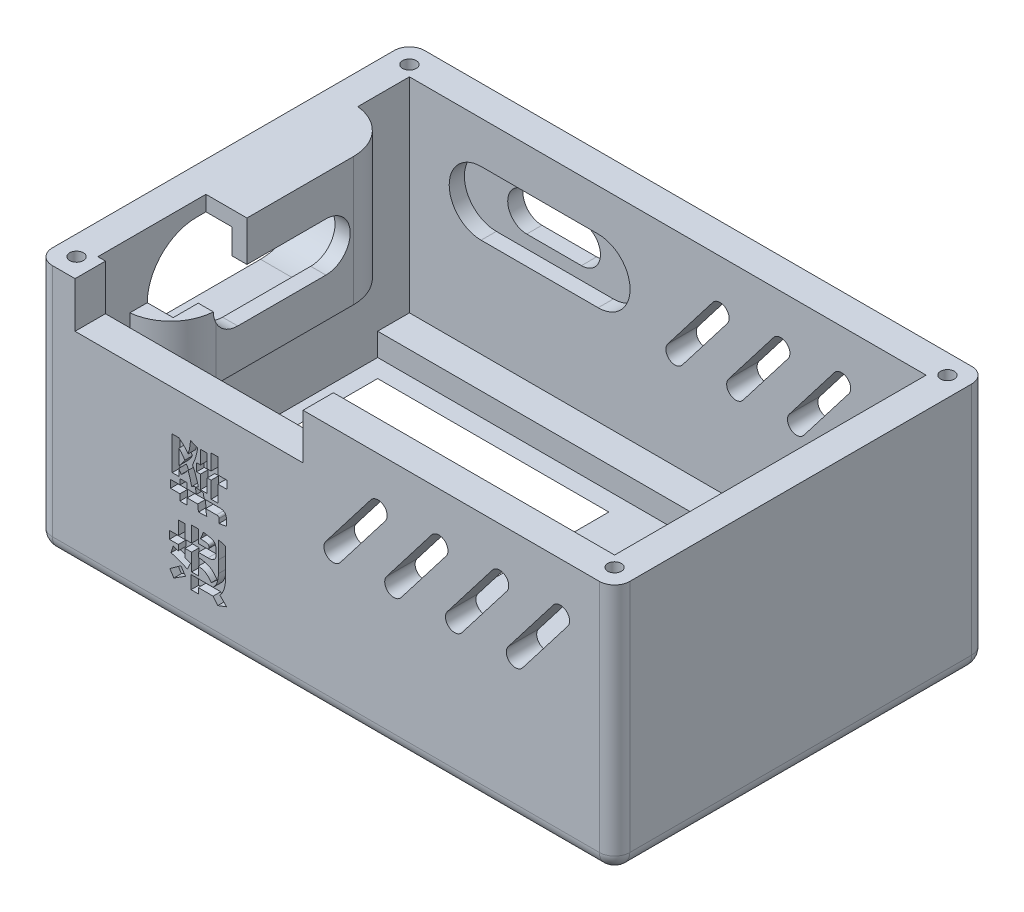
SolidWorks part; units mm, degrees
material "尼龙 6/10"
ref_plane "前视基准面" through (0, 0, 0) normal (0, 0, 1) x (1, 0, 0)
ref_plane "上视基准面" through (0, 0, 0) normal (0, 1, 0) x (1, 0, 0)
ref_plane "右视基准面" through (0, 0, 0) normal (1, 0, 0) x (0, 0, -1)
sketch "草图1" plane through (0, 0, 0) normal (0, 1, 0) x (1, 0, 0)
  line L1 (-72.1576, -30.7504) -> (-34.1576, -30.7504)
  line L2 (-72.1576, -30.7504) -> (-72.1576, -6.2504)
  line L3 (-72.1576, -6.2504) -> (-34.1576, -6.2504)
  line L4 (-34.1576, -30.7504) -> (-34.1576, -6.2504)
  dimension "D1" = 24.5
  dimension "D2" = 38
extrude "凸台-拉伸1" add sketch "草图1" along normal blind 16.45 contours L2 L1 L4 L3
sketch "草图2" plane through (0, 16.45, 0) normal (0, 1, 0) x (1, 0, 0)
  line L0 (-34.1576, -30.7504) -> (-34.1576, -6.2504) construction
  line L1 (-70.1576, -8.2504) -> (-36.1576, -8.2504)
  line L2 (-70.1576, -8.2504) -> (-70.1576, -28.7504)
  line L3 (-70.1576, -28.7504) -> (-36.1576, -28.7504)
  line L4 (-36.1576, -8.2504) -> (-36.1576, -28.7504)
  line L5 (-72.1576, -30.7504) -> (-34.1576, -30.7504) construction
  line L6 (-72.1576, -30.7504) -> (-72.1576, -6.2504) construction
  line L7 (-72.1576, -6.2504) -> (-34.1576, -6.2504) construction
  dimension "D1" = 2
  dimension "D2" = 2
  dimension "D3" = 2
  dimension "D4" = 2
extrude "切除-拉伸1" cut sketch "草图2" against normal blind 13.45
sketch "草图4" plane through (0, 0, 0) normal (0, -1, 0) x (-1, 0, 0)
  line L0 (72.1576, -30.7504) -> (72.1576, -6.2504) construction
  line L1 (68.9576, -11.5404) -> (53.7476, -11.5404)
  line L2 (68.9576, -11.5404) -> (68.9576, -26.7504)
  line L3 (68.9576, -26.7504) -> (53.7476, -26.7504)
  line L4 (53.7476, -11.5404) -> (53.7476, -26.7504)
  line L6 (72.1576, -30.7504) -> (34.1576, -30.7504) construction
  dimension "D1" = 15.21
  dimension "D2" = 15.21
  dimension "D3" = 3.2
  dimension "D4" = 4
extrude "切除-拉伸2" cut sketch "草图4" against normal blind 15 contours L2 L1 L4 L3
sketch "草图6" plane through (0, 0, 30.7504) normal (0, 0, 1) x (1, 0, 0)
  line L1 (-54.6576, 13.45) -> (-69.6576, 13.45)
  line L2 (-54.6576, 13.45) -> (-54.6576, 16.45)
  line L3 (-54.6576, 16.45) -> (-69.6576, 16.45)
  line L4 (-69.6576, 13.45) -> (-69.6576, 16.45)
  line L5 (-72.1576, 16.45) -> (-72.1576, 0) construction
  line L6 (-72.1576, 16.45) -> (-34.1576, 16.45) construction
  point P9 (-69.6576, 14.95)
  dimension "D2" = 3
  dimension "D3" = 2.5
  dimension "D4" = 15
extrude "切除-拉伸4" cut sketch "草图6" against normal blind 5
sketch "草图11" plane through (0, 3, 0) normal (0, 1, 0) x (1, 0, 0)
  line L0 (-68.9576, -26.7504) -> (-68.9576, -11.5404) construction
  line L1 (-37.6576, -10.3404) -> (-70.1576, -10.3404)
  line L2 (-37.6576, -10.3404) -> (-37.6576, -27.9404)
  line L3 (-37.6576, -27.9404) -> (-70.1576, -27.9404)
  line L4 (-70.1576, -10.3404) -> (-70.1576, -27.9404)
  line L5 (-53.7476, -11.5404) -> (-68.9576, -11.5404) construction
  line L7 (-36.1576, -28.7504) -> (-36.1576, -8.2504) construction
  dimension "D1" = 1.5
  dimension "D2" = 17.6
  dimension "D3" = 1.2
  dimension "D4" = 1.2
extrude "切除-拉伸10" cut sketch "草图11" against normal blind 1.5
fillet "圆角2" radius 1 8 edges at (-34.1576, 8.225, 6.2504) (-53.1576, 0, 6.2504) (-53.1576, 0, 30.7504) (-72.1576, 0, 18.5004) (-72.1576, 8.225, 30.7504) (-34.1576, 8.225, 30.7504) (-34.1576, 0, 18.5004) (-72.1576, 8.225, 6.2504)
chamfer "倒角2" distance 1.5 distance2 1.5 4 edges at (-61.3526, 0, 26.7504) (-53.7476, 0, 19.1454) (-61.3526, 0, 11.5404) (-68.9576, 0, 19.1454)
fillet "圆角8" radius 1 1 edges at (-37.6576, 3, 19.1404) type face fillet first side face at (-37.6576, 2.25, 19.1404) second side face at (-53.5326, 3, 18.8204)
sketch "草图24" plane through (-36.1576, 0, 0) normal (-1, 0, 0) x (0, 0, 1)
  line L1 (22.6404, 3) -> (15.6404, 3)
  line L2 (22.6404, 3) -> (22.6404, 12.5)
  line L3 (22.6404, 12.5) -> (15.6404, 12.5)
  line L4 (15.6404, 3) -> (15.6404, 12.5)
  line L10 (10.3404, 3) -> (27.9404, 3) construction
  point P4 (19.1404, 3)
  dimension "D1" = 9.5
  dimension "D2" = 7
extrude "切除-拉伸17" cut sketch "草图24" against normal blind 1
sketch "草图29" plane through (0, 16.45, 0) normal (0, 1, 0) x (1, 0, 0)
  line L0 (-72.1576, -29.7504) -> (-72.1576, -7.2504) construction
  line L4 (-34.1576, -29.7504) -> (-34.1576, -7.2504) construction
  line L5 (-71.1576, -30.7504) -> (-69.6576, -30.7504) construction
  line L8 (-71.1576, -6.2504) -> (-35.1576, -6.2504) construction
  circle A0 centre (-70.8576, -7.5504) radius 0.45
  circle A1 centre (-70.8576, -29.4504) radius 0.45
  circle A2 centre (-35.4576, -7.5504) radius 0.45
  circle A3 centre (-35.4576, -29.4504) radius 0.45
  dimension "D1" = 0.9
  dimension "D2" = 1.3
  dimension "D3" = 1.3
  dimension "D4" = 1.3
  dimension "D5" = 1.3
extrude "切除-拉伸18" cut sketch "草图29" against normal blind 6
sketch "草图32" plane through (0, 0, 8.2504) normal (0, 0, 1) x (1, 0, 0)
  line L0 (-57.7394, 11.6) -> (-65.4394, 11.6) construction
  line L1 (-57.7394, 9.5) -> (-65.4394, 9.5)
  line L2 (-57.7394, 13.7) -> (-65.4394, 13.7)
  line L4 (-36.1576, 3) -> (-70.1576, 3) construction
  arc A0 (-57.7394, 9.5) -> (-57.7394, 13.7) centre (-57.7394, 11.6) ccw
  arc A1 (-65.4394, 13.7) -> (-65.4394, 9.5) centre (-65.4394, 11.6) ccw
  point P2 (-61.5894, 11.6)
  dimension "D1" = 7.7
  dimension "D2" = 4.2
  dimension "D3" = 6.5
extrude "切除-拉伸19" cut sketch "草图32" against normal blind 1 contours L1 A1 L2 A0
sketch "草图33" plane through (0, 0, 7.2504) normal (0, 0, 1) x (1, 0, 0)
  line L0 (-63.4394, 12.85) -> (-59.8394, 12.85)
  line L1 (-59.8394, 10.35) -> (-63.4394, 10.35)
  line L6 (-57.7394, 13.7) -> (-65.4394, 13.7) construction
  arc A0 (-59.8394, 10.35) -> (-59.8394, 12.85) centre (-59.8394, 11.6) ccw
  arc A1 (-63.4394, 12.85) -> (-63.4394, 10.35) centre (-63.4394, 11.6) ccw
  arc A3 (-65.4394, 13.7) -> (-65.4394, 9.5) centre (-65.4394, 11.6) ccw construction
  dimension "D2" = 3.6
  dimension "D5" = 1.25
  dimension "D6" = 1.25
  dimension "D1" = 2.5
  dimension "D3" = 2
  dimension "D4" = 0.85
extrude "切除-拉伸20" cut sketch "草图33" against normal up to next
sketch "草图37" plane through (0, 16.45, 0) normal (0, 1, 0) x (1, 0, 0)
  line L1 (-70.4576, -11.6454) -> (-67.4576, -11.6454)
  line L2 (-70.4576, -11.6454) -> (-70.4576, -26.6454)
  line L3 (-70.4576, -26.6454) -> (-67.4576, -26.6454)
  line L4 (-67.4576, -11.6454) -> (-67.4576, -26.6454)
  line L5 (-70.4576, -10.0404) -> (-70.4576, -28.2504) construction
  point P4 (-70.4576, -19.1454)
  dimension "D1" = 3
  dimension "D2" = 15
extrude "凸台-拉伸8" add sketch "草图37" against normal blind 10
sketch "草图34" plane through (-72.1576, 0, 0) normal (-1, 0, 0) x (0, 0, 1)
  line L0 (22.2454, 12.2) -> (16.0454, 12.2) construction
  line L3 (22.2454, 8.95) -> (16.0454, 8.95)
  line L4 (22.2454, 15.45) -> (16.0454, 15.45)
  line L5 (10.0404, 0) -> (28.2504, 0) construction
  line L7 (29.7504, 16.45) -> (7.2504, 16.45) construction
  line L12 (7.2504, 1) -> (29.7504, 1) construction
  arc A2 (22.2454, 8.95) -> (22.2454, 15.45) centre (22.2454, 12.2) ccw
  arc A3 (16.0454, 15.45) -> (16.0454, 8.95) centre (16.0454, 12.2) ccw
  point P3 (19.1454, 12.2)
  point P8 (19.1454, 15.45)
  point P15 (18.5004, 1)
  point P19 (19.1454, 0)
  dimension "D3" = 1
  dimension "D1" = 6.2
  dimension "D2" = 6.5
extrude "切除-拉伸21" cut sketch "草图34" against normal blind 3.7
sketch "草图39" plane through (-68.4576, 0, 0) normal (-1, 0, 0) x (0, 0, 1)
  line L0 (22.2454, 12.2) -> (16.4454, 12.2) construction
  line L1 (22.2454, 10.6) -> (16.4454, 10.6)
  line L2 (22.2454, 13.8) -> (16.4454, 13.8)
  line L4 (22.2454, 15.45) -> (16.0454, 15.45) construction
  line L5 (16.0454, 8.95) -> (22.2454, 8.95) construction
  arc A0 (22.2454, 10.6) -> (22.2454, 13.8) centre (22.2454, 12.2) ccw
  arc A1 (16.4454, 13.8) -> (16.4454, 10.6) centre (16.4454, 12.2) ccw
  point P2 (19.3454, 12.2)
  point P7 (23.8454, 12.2)
  point P8 (14.8454, 12.2)
  dimension "D1" = 3.2
  dimension "D2" = 9
extrude "切除-拉伸24" cut sketch "草图39" against normal blind 9 contours L1 A1 L2 A0
fillet "圆角9" radius 3 2 edges at (-67.4576, 11.45, 11.6454) (-67.4576, 11.45, 26.6454)
sketch "草图42" plane through (0, 0, 6.2504) normal (0, 0, -1) x (-1, 0, 0)
  line L0 (72.1576, 16.45) -> (72.1576, 1) construction
  text T0 "<b><r270>确</r></b>" font "微软雅黑" height 3
  text T1 "<b><r270>认</r></b>" font "微软雅黑" height 3
  dimension "D1" = 12
extrude "切除-拉伸26" cut sketch "草图42" against normal blind 0.5
sketch "草图43" plane through (0, 0, 30.7504) normal (0, 0, 1) x (1, 0, 0)
  line L0 (-71.1576, 16.45) -> (-71.1576, 1) construction
  text T0 "<b><r90>选</r></b>" font "微软雅黑" height 3
  text T1 "<b><r90>择</r></b>" font "微软雅黑" height 3
  dimension "D1" = 11
extrude "切除-拉伸27" cut sketch "草图43" against normal blind 0.5
sketch "草图46" plane through (-67.4576, 0, 0) normal (1, 0, 0) x (0, 0, -1)
  line L19 (-26.6454, 8) -> (-11.6454, 8)
  line L20 (-26.6454, 8) -> (-26.6454, 3)
  line L21 (-26.6454, 3) -> (-11.6454, 3)
  line L22 (-11.6454, 8) -> (-11.6454, 3)
  line L25 (-8.2504, 3) -> (-10.3404, 3) construction
  dimension "D1" = 5
extrude "切除-拉伸29" cut sketch "草图46" against normal up to surface (2.7 mm away) and the other way up to surface (31.3 mm away) up to face at (-70.1576, 7.8083, 18.9288) other way up to face at (-36.1576, 8.7375, 18.8204)
sketch "草图48" plane through (0, 1.5, 0) normal (0, 1, 0) x (1, 0, 0)
  line L0 (-70.1576, -8.2504) -> (-70.1576, -10.3404) construction
  line L1 (-49.3076, -10.9679) -> (-47.5264, -10.9679)
  line L2 (-49.3076, -10.9679) -> (-49.3076, -12.9679)
  line L3 (-49.3076, -12.9679) -> (-47.5264, -12.9679)
  line L4 (-47.5264, -10.9679) -> (-47.5264, -12.9679)
  line L5 (-49.3076, -25.3179) -> (-47.5264, -25.3179)
  line L6 (-49.3076, -25.3179) -> (-49.3076, -27.3179)
  line L7 (-49.3076, -27.3179) -> (-47.5264, -27.3179)
  line L8 (-47.5264, -25.3179) -> (-47.5264, -27.3179)
  dimension "D1" = 20.85
  dimension "D2" = 2
  dimension "D3" = 12.35
extrude "凸台-拉伸9" add sketch "草图48" along normal blind 1.4
sketch "草图49" plane through (0, 3, 0) normal (0, 1, 0) x (1, 0, 0)
  line L1 (-36.6576, -15.6404) -> (-37.6576, -15.6404)
  line L2 (-36.6576, -15.6404) -> (-36.6576, -22.6404)
  line L3 (-36.6576, -22.6404) -> (-37.6576, -22.6404)
  line L4 (-37.6576, -15.6404) -> (-37.6576, -22.6404)
  line L5 (-37.6576, -27.9404) -> (-37.6576, -10.3404) construction
  line L11 (-36.6576, -10.3404) -> (-36.6576, -27.9404) construction
  point P4 (-36.6576, -19.1404)
  dimension "D1" = 7
extrude "切除-拉伸30" cut sketch "草图49" against normal up to surface (1.5 mm away) up to face at (-48.417, 1.5, 11.9679)
sketch "草图50" plane through (0, 0, 6.2504) normal (0, 0, -1) x (-1, 0, 0)
  line L0 (49.7213, 13.2108) -> (52.6822, 9.3661) construction
  line L1 (50.1967, 13.5769) -> (53.1576, 9.7322)
  line L2 (49.2459, 12.8448) -> (52.2068, 9)
  line L3 (45.7213, 13.2108) -> (48.6822, 9.3661) construction
  line L4 (46.1967, 13.5769) -> (49.1576, 9.7322)
  line L5 (45.2459, 12.8448) -> (48.2068, 9)
  line L6 (41.7213, 13.2108) -> (44.6822, 9.3661) construction
  line L7 (42.1967, 13.5769) -> (45.1576, 9.7322)
  line L8 (41.2459, 12.8448) -> (44.2068, 9)
  line L9 (37.7213, 13.2108) -> (40.6822, 9.3661) construction
  line L10 (38.1967, 13.5769) -> (41.1576, 9.7322)
  line L11 (37.2459, 12.8448) -> (40.2068, 9)
  line L12 (71.1576, 1) -> (71.1576, 16.45) construction
  line L13 (35.1576, 1) -> (71.1576, 1) construction
  arc A0 (50.1967, 13.5769) -> (49.2459, 12.8448) centre (49.7213, 13.2108) ccw
  arc A1 (52.2068, 9) -> (53.1576, 9.7322) centre (52.6822, 9.3661) ccw
  arc A2 (46.1967, 13.5769) -> (45.2459, 12.8448) centre (45.7213, 13.2108) ccw
  arc A3 (48.2068, 9) -> (49.1576, 9.7322) centre (48.6822, 9.3661) ccw
  arc A4 (42.1967, 13.5769) -> (41.2459, 12.8448) centre (41.7213, 13.2108) ccw
  arc A5 (44.2068, 9) -> (45.1576, 9.7322) centre (44.6822, 9.3661) ccw
  arc A6 (38.1967, 13.5769) -> (37.2459, 12.8448) centre (37.7213, 13.2108) ccw
  arc A7 (40.2068, 9) -> (41.1576, 9.7322) centre (40.6822, 9.3661) ccw
  point P2 (51.2018, 11.2885)
  point P11 (47.2018, 11.2885)
  point P18 (43.2018, 11.2885)
  point P25 (39.2018, 11.2885)
  dimension "D4" = 4.8527
  dimension "D2" = 18
  dimension "D3" = 8
  dimension "D1" = 4
extrude "切除-拉伸31" cut sketch "草图50" against normal through all
sketch "草图51" plane through (0, 0, 0) normal (0, -1, 0) x (1, 0, 0)
  line L0 (-50.2476, 28.2504) -> (-48.2476, 28.2504)
  line L1 (-39.1576, 28.2504) -> (-37.1576, 28.2504)
  line L2 (-39.1576, 28.2504) -> (-39.1576, 9.2504)
  line L3 (-39.1576, 9.2504) -> (-37.1576, 9.2504)
  line L4 (-37.1576, 28.2504) -> (-37.1576, 9.2504)
  line L5 (-50.2476, 28.2504) -> (-50.2476, 9.2504)
  line L6 (-50.2476, 9.2504) -> (-48.2476, 9.2504)
  line L7 (-48.2476, 28.2504) -> (-48.2476, 9.2504)
  line L8 (-52.2476, 28.2504) -> (-52.2476, 10.0404) construction
  line L9 (-35.1576, 7.2504) -> (-35.1576, 29.7504) construction
  line L10 (-71.1576, 7.2504) -> (-35.1576, 7.2504) construction
  line L11 (-70.4576, 28.2504) -> (-52.2476, 28.2504) construction
  dimension "D1" = 2
  dimension "D2" = 2
  dimension "D4" = 2
  dimension "D5" = 2
extrude "切除-拉伸32" cut sketch "草图51" against normal blind 0.5
sketch "草图52" plane through (0, 0.5, 0) normal (0, -1, 0) x (1, 0, 0)
  line L0 (-50.2476, 28.2504) -> (-50.2476, 9.2504) construction
  line L1 (-50.2476, 27.9504) -> (-48.2476, 27.9504)
  line L2 (-50.2476, 27.9504) -> (-50.2476, 27.4504)
  line L3 (-50.2476, 27.4504) -> (-48.2476, 27.4504)
  line L4 (-48.2476, 27.9504) -> (-48.2476, 27.4504)
  line L5 (-48.2476, 9.2504) -> (-48.2476, 28.2504) construction
  line L6 (-48.2476, 28.2504) -> (-50.2476, 28.2504) construction
  line L7 (-39.1576, 27.9504) -> (-39.1576, 27.4504)
  line L8 (-39.1576, 27.9504) -> (-37.1576, 27.9504)
  line L9 (-37.1576, 27.9504) -> (-37.1576, 27.4504)
  line L10 (-39.1576, 27.4504) -> (-37.1576, 27.4504)
  line L11 (-39.1576, 27.1231) -> (-39.1576, 26.6231)
  line L12 (-39.1576, 27.1231) -> (-37.1576, 27.1231)
  line L13 (-37.1576, 27.1231) -> (-37.1576, 26.6231)
  line L14 (-39.1576, 26.6231) -> (-37.1576, 26.6231)
  line L15 (-39.1576, 26.2959) -> (-39.1576, 25.7959)
  line L16 (-39.1576, 26.2959) -> (-37.1576, 26.2959)
  line L17 (-37.1576, 26.2959) -> (-37.1576, 25.7959)
  line L18 (-39.1576, 25.7959) -> (-37.1576, 25.7959)
  line L19 (-39.1576, 25.4686) -> (-39.1576, 24.9686)
  line L20 (-39.1576, 25.4686) -> (-37.1576, 25.4686)
  line L21 (-37.1576, 25.4686) -> (-37.1576, 24.9686)
  line L22 (-39.1576, 24.9686) -> (-37.1576, 24.9686)
  line L23 (-39.1576, 24.6413) -> (-39.1576, 24.1413)
  line L24 (-39.1576, 24.6413) -> (-37.1576, 24.6413)
  line L25 (-37.1576, 24.6413) -> (-37.1576, 24.1413)
  line L26 (-39.1576, 24.1413) -> (-37.1576, 24.1413)
  line L27 (-39.1576, 23.8141) -> (-39.1576, 23.3141)
  line L28 (-39.1576, 23.8141) -> (-37.1576, 23.8141)
  line L29 (-37.1576, 23.8141) -> (-37.1576, 23.3141)
  line L30 (-39.1576, 23.3141) -> (-37.1576, 23.3141)
  line L31 (-39.1576, 22.9868) -> (-39.1576, 22.4868)
  line L32 (-39.1576, 22.9868) -> (-37.1576, 22.9868)
  line L33 (-37.1576, 22.9868) -> (-37.1576, 22.4868)
  line L34 (-39.1576, 22.4868) -> (-37.1576, 22.4868)
  line L35 (-39.1576, 22.1595) -> (-39.1576, 21.6595)
  line L36 (-39.1576, 22.1595) -> (-37.1576, 22.1595)
  line L37 (-37.1576, 22.1595) -> (-37.1576, 21.6595)
  line L38 (-39.1576, 21.6595) -> (-37.1576, 21.6595)
  line L39 (-39.1576, 21.3322) -> (-39.1576, 20.8322)
  line L40 (-39.1576, 21.3322) -> (-37.1576, 21.3322)
  line L41 (-37.1576, 21.3322) -> (-37.1576, 20.8322)
  line L42 (-39.1576, 20.8322) -> (-37.1576, 20.8322)
  line L43 (-39.1576, 20.505) -> (-39.1576, 20.005)
  line L44 (-39.1576, 20.505) -> (-37.1576, 20.505)
  line L45 (-37.1576, 20.505) -> (-37.1576, 20.005)
  line L46 (-39.1576, 20.005) -> (-37.1576, 20.005)
  line L47 (-39.1576, 19.6777) -> (-39.1576, 19.1777)
  line L48 (-39.1576, 19.6777) -> (-37.1576, 19.6777)
  line L49 (-37.1576, 19.6777) -> (-37.1576, 19.1777)
  line L50 (-39.1576, 19.1777) -> (-37.1576, 19.1777)
  line L51 (-39.1576, 18.8504) -> (-39.1576, 18.3504)
  line L52 (-39.1576, 18.8504) -> (-37.1576, 18.8504)
  line L53 (-37.1576, 18.8504) -> (-37.1576, 18.3504)
  line L54 (-39.1576, 18.3504) -> (-37.1576, 18.3504)
  line L55 (-39.1576, 18.0231) -> (-39.1576, 17.5231)
  line L56 (-39.1576, 18.0231) -> (-37.1576, 18.0231)
  line L57 (-37.1576, 18.0231) -> (-37.1576, 17.5231)
  line L58 (-39.1576, 17.5231) -> (-37.1576, 17.5231)
  line L59 (-39.1576, 17.1959) -> (-39.1576, 16.6959)
  line L60 (-39.1576, 17.1959) -> (-37.1576, 17.1959)
  line L61 (-37.1576, 17.1959) -> (-37.1576, 16.6959)
  line L62 (-39.1576, 16.6959) -> (-37.1576, 16.6959)
  line L63 (-39.1576, 16.3686) -> (-39.1576, 15.8686)
  line L64 (-39.1576, 16.3686) -> (-37.1576, 16.3686)
  line L65 (-37.1576, 16.3686) -> (-37.1576, 15.8686)
  line L66 (-39.1576, 15.8686) -> (-37.1576, 15.8686)
  line L67 (-39.1576, 15.5413) -> (-39.1576, 15.0413)
  line L68 (-39.1576, 15.5413) -> (-37.1576, 15.5413)
  line L69 (-37.1576, 15.5413) -> (-37.1576, 15.0413)
  line L70 (-39.1576, 15.0413) -> (-37.1576, 15.0413)
  line L71 (-39.1576, 14.7141) -> (-39.1576, 14.2141)
  line L72 (-39.1576, 14.7141) -> (-37.1576, 14.7141)
  line L73 (-37.1576, 14.7141) -> (-37.1576, 14.2141)
  line L74 (-39.1576, 14.2141) -> (-37.1576, 14.2141)
  line L75 (-50.2476, 27.1231) -> (-50.2476, 26.6231)
  line L76 (-50.2476, 27.1231) -> (-48.2476, 27.1231)
  line L77 (-48.2476, 27.1231) -> (-48.2476, 26.6231)
  line L78 (-50.2476, 26.6231) -> (-48.2476, 26.6231)
  line L79 (-50.2476, 26.2959) -> (-50.2476, 25.7959)
  line L80 (-50.2476, 26.2959) -> (-48.2476, 26.2959)
  line L81 (-48.2476, 26.2959) -> (-48.2476, 25.7959)
  line L82 (-50.2476, 25.7959) -> (-48.2476, 25.7959)
  line L83 (-50.2476, 25.4686) -> (-50.2476, 24.9686)
  line L84 (-50.2476, 25.4686) -> (-48.2476, 25.4686)
  line L85 (-48.2476, 25.4686) -> (-48.2476, 24.9686)
  line L86 (-50.2476, 24.9686) -> (-48.2476, 24.9686)
  line L87 (-50.2476, 24.6413) -> (-50.2476, 24.1413)
  line L88 (-50.2476, 24.6413) -> (-48.2476, 24.6413)
  line L89 (-48.2476, 24.6413) -> (-48.2476, 24.1413)
  line L90 (-50.2476, 24.1413) -> (-48.2476, 24.1413)
  line L91 (-50.2476, 23.8141) -> (-50.2476, 23.3141)
  line L92 (-50.2476, 23.8141) -> (-48.2476, 23.8141)
  line L93 (-48.2476, 23.8141) -> (-48.2476, 23.3141)
  line L94 (-50.2476, 23.3141) -> (-48.2476, 23.3141)
  line L95 (-50.2476, 22.9868) -> (-50.2476, 22.4868)
  line L96 (-50.2476, 22.9868) -> (-48.2476, 22.9868)
  line L97 (-48.2476, 22.9868) -> (-48.2476, 22.4868)
  line L98 (-50.2476, 22.4868) -> (-48.2476, 22.4868)
  line L99 (-50.2476, 22.1595) -> (-50.2476, 21.6595)
  line L100 (-50.2476, 22.1595) -> (-48.2476, 22.1595)
  line L101 (-48.2476, 22.1595) -> (-48.2476, 21.6595)
  line L102 (-50.2476, 21.6595) -> (-48.2476, 21.6595)
  line L103 (-50.2476, 21.3322) -> (-50.2476, 20.8322)
  line L104 (-50.2476, 21.3322) -> (-48.2476, 21.3322)
  line L105 (-48.2476, 21.3322) -> (-48.2476, 20.8322)
  line L106 (-50.2476, 20.8322) -> (-48.2476, 20.8322)
  line L107 (-50.2476, 20.505) -> (-50.2476, 20.005)
  line L108 (-50.2476, 20.505) -> (-48.2476, 20.505)
  line L109 (-48.2476, 20.505) -> (-48.2476, 20.005)
  line L110 (-50.2476, 20.005) -> (-48.2476, 20.005)
  line L111 (-50.2476, 19.6777) -> (-50.2476, 19.1777)
  line L112 (-50.2476, 19.6777) -> (-48.2476, 19.6777)
  line L113 (-48.2476, 19.6777) -> (-48.2476, 19.1777)
  line L114 (-50.2476, 19.1777) -> (-48.2476, 19.1777)
  line L115 (-50.2476, 18.8504) -> (-50.2476, 18.3504)
  line L116 (-50.2476, 18.8504) -> (-48.2476, 18.8504)
  line L117 (-48.2476, 18.8504) -> (-48.2476, 18.3504)
  line L118 (-50.2476, 18.3504) -> (-48.2476, 18.3504)
  line L119 (-50.2476, 18.0231) -> (-50.2476, 17.5231)
  line L120 (-50.2476, 18.0231) -> (-48.2476, 18.0231)
  line L121 (-48.2476, 18.0231) -> (-48.2476, 17.5231)
  line L122 (-50.2476, 17.5231) -> (-48.2476, 17.5231)
  line L123 (-50.2476, 17.1959) -> (-50.2476, 16.6959)
  line L124 (-50.2476, 17.1959) -> (-48.2476, 17.1959)
  line L125 (-48.2476, 17.1959) -> (-48.2476, 16.6959)
  line L126 (-50.2476, 16.6959) -> (-48.2476, 16.6959)
  line L127 (-50.2476, 16.3686) -> (-50.2476, 15.8686)
  line L128 (-50.2476, 16.3686) -> (-48.2476, 16.3686)
  line L129 (-48.2476, 16.3686) -> (-48.2476, 15.8686)
  line L130 (-50.2476, 15.8686) -> (-48.2476, 15.8686)
  line L131 (-50.2476, 15.5413) -> (-50.2476, 15.0413)
  line L132 (-50.2476, 15.5413) -> (-48.2476, 15.5413)
  line L133 (-48.2476, 15.5413) -> (-48.2476, 15.0413)
  line L134 (-50.2476, 15.0413) -> (-48.2476, 15.0413)
  line L135 (-50.2476, 14.7141) -> (-50.2476, 14.2141)
  line L136 (-50.2476, 14.7141) -> (-48.2476, 14.7141)
  line L137 (-48.2476, 14.7141) -> (-48.2476, 14.2141)
  line L138 (-50.2476, 14.2141) -> (-48.2476, 14.2141)
  line L139 (-50.2476, 13.8868) -> (-50.2476, 13.3868)
  line L140 (-50.2476, 13.8868) -> (-48.2476, 13.8868)
  line L141 (-48.2476, 13.8868) -> (-48.2476, 13.3868)
  line L142 (-50.2476, 13.3868) -> (-48.2476, 13.3868)
  line L143 (-39.1576, 13.8868) -> (-39.1576, 13.3868)
  line L144 (-39.1576, 13.8868) -> (-37.1576, 13.8868)
  line L145 (-37.1576, 13.8868) -> (-37.1576, 13.3868)
  line L146 (-39.1576, 13.3868) -> (-37.1576, 13.3868)
  line L147 (-50.2476, 13.0595) -> (-50.2476, 12.5595)
  line L148 (-50.2476, 13.0595) -> (-48.2476, 13.0595)
  line L149 (-48.2476, 13.0595) -> (-48.2476, 12.5595)
  line L150 (-50.2476, 12.5595) -> (-48.2476, 12.5595)
  line L151 (-39.1576, 13.0595) -> (-39.1576, 12.5595)
  line L152 (-39.1576, 13.0595) -> (-37.1576, 13.0595)
  line L153 (-37.1576, 13.0595) -> (-37.1576, 12.5595)
  line L154 (-39.1576, 12.5595) -> (-37.1576, 12.5595)
  line L155 (-50.2476, 12.2322) -> (-50.2476, 11.7322)
  line L156 (-50.2476, 12.2322) -> (-48.2476, 12.2322)
  line L157 (-48.2476, 12.2322) -> (-48.2476, 11.7322)
  line L158 (-50.2476, 11.7322) -> (-48.2476, 11.7322)
  line L159 (-39.1576, 12.2322) -> (-39.1576, 11.7322)
  line L160 (-39.1576, 12.2322) -> (-37.1576, 12.2322)
  line L161 (-37.1576, 12.2322) -> (-37.1576, 11.7322)
  line L162 (-39.1576, 11.7322) -> (-37.1576, 11.7322)
  line L163 (-50.2476, 11.405) -> (-50.2476, 10.905)
  line L164 (-50.2476, 11.405) -> (-48.2476, 11.405)
  line L165 (-48.2476, 11.405) -> (-48.2476, 10.905)
  line L166 (-50.2476, 10.905) -> (-48.2476, 10.905)
  line L167 (-39.1576, 11.405) -> (-39.1576, 10.905)
  line L168 (-39.1576, 11.405) -> (-37.1576, 11.405)
  line L169 (-37.1576, 11.405) -> (-37.1576, 10.905)
  line L170 (-39.1576, 10.905) -> (-37.1576, 10.905)
  line L171 (-50.2476, 10.5777) -> (-50.2476, 10.0777)
  line L172 (-50.2476, 10.5777) -> (-48.2476, 10.5777)
  line L173 (-48.2476, 10.5777) -> (-48.2476, 10.0777)
  line L174 (-50.2476, 10.0777) -> (-48.2476, 10.0777)
  line L175 (-39.1576, 10.5777) -> (-39.1576, 10.0777)
  line L176 (-39.1576, 10.5777) -> (-37.1576, 10.5777)
  line L177 (-37.1576, 10.5777) -> (-37.1576, 10.0777)
  line L178 (-39.1576, 10.0777) -> (-37.1576, 10.0777)
  line L179 (-50.2476, 9.7504) -> (-50.2476, 9.2504)
  line L180 (-50.2476, 9.7504) -> (-48.2476, 9.7504)
  line L181 (-48.2476, 9.7504) -> (-48.2476, 9.2504)
  line L182 (-50.2476, 9.2504) -> (-48.2476, 9.2504)
  line L183 (-39.1576, 9.7504) -> (-39.1576, 9.2504)
  line L184 (-39.1576, 9.7504) -> (-37.1576, 9.7504)
  line L185 (-37.1576, 9.7504) -> (-37.1576, 9.2504)
  line L186 (-39.1576, 9.2504) -> (-37.1576, 9.2504)
  line L187 (-39.1576, 28.2504) -> (-39.1576, 9.2504) construction
  line L188 (-39.1576, 9.2504) -> (-37.1576, 9.2504) construction
  dimension "D1" = 0.5
  dimension "D2" = 0.3
  dimension "D3" = 2
  dimension "D4" = 23
extrude "凸台-拉伸10" add sketch "草图52" along normal blind 0.5
sketch "草图53" plane through (0, 16.45, 0) normal (0, 1, 0) x (1, 0, 0)
  line L1 (-70.1576, -21.6396) -> (-67.4576, -21.6396)
  line L2 (-70.1576, -21.6396) -> (-70.1576, -26.6454)
  line L3 (-70.1576, -26.6454) -> (-67.4576, -26.6454)
  line L4 (-67.4576, -21.6396) -> (-67.4576, -26.6454)
  line L7 (-67.4576, -23.6605) -> (-67.4576, -14.6304) construction
  line L8 (-70.1576, -26.6454) -> (-70.1576, -28.7504) construction
extrude "切除-拉伸33" cut sketch "草图53" against normal blind 4.25
sketch "草图54" plane through (0, 0, 0) normal (0, -1, 0) x (-1, 0, 0)
  line L0 (44.3147, -24.5348) -> (44.3147, -23.5348)
  line L1 (46.3147, -25.5348) -> (44.3147, -25.5348)
  line L2 (46.3147, -25.5348) -> (46.3147, -24.5348)
  line L3 (46.3147, -24.5348) -> (44.3147, -24.5348)
  line L4 (41.3147, -25.5348) -> (41.3147, -24.5348)
  line L5 (44.3147, -26.5348) -> (43.3147, -26.5348)
  line L6 (44.3147, -26.5348) -> (44.3147, -25.5348)
  line L7 (44.3147, -23.5348) -> (43.3147, -23.5348)
  line L8 (43.3147, -26.5348) -> (43.3147, -25.5348)
  line L9 (43.3147, -24.5348) -> (43.3147, -23.5348)
  line L10 (43.3147, -25.5348) -> (41.3147, -25.5348)
  line L11 (43.3147, -24.5348) -> (41.3147, -24.5348)
  circle A0 centre (43.8147, -13.4351) radius 2
  point P14 (43.8147, -23.5348)
  dimension "D1" = 4
  dimension "D2" = 1
  dimension "D3" = 1
  dimension "D4" = 2
  dimension "D5" = 2
  dimension "D6" = 1
  dimension "D7" = 1
extrude "切除-拉伸34" cut sketch "草图54" against normal blind 0.5
